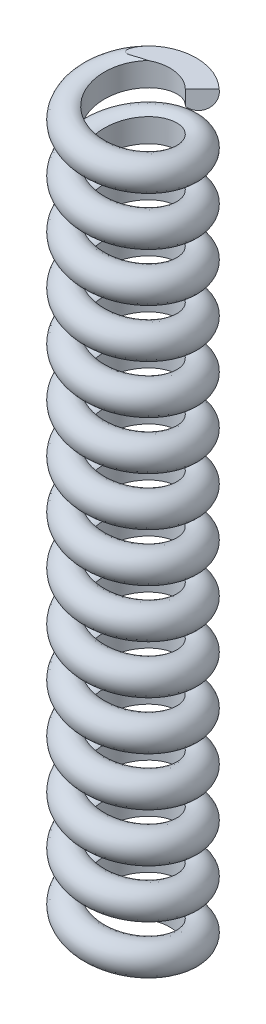
SolidWorks part; units mm, degrees
note: '?' marks a value the reader was unsure of.
material "1023 Carbon Steel Sheet (SS)"
ref_plane "Front" through (0, 0, 0) normal (0, 0, 1) x (1, 0, 0)
ref_plane "Top" through (0, 0, 0) normal (0, 1, 0) x (1, 0, 0)
ref_plane "Right" through (0, 0, 0) normal (1, 0, 0) x (0, 0, -1)
sketch "Sketch1" plane through (0, 0, 0) normal (0, 1, 0) x (1, 0, 0)
  circle A0 centre (0, 0) radius 3.9688
  point P4 (0, 0)
  dimension "D1" = 7.9375
curve "Helix/Spiral1" pitch 4.1639 height 63.5 turns 15.25
sweep "Sweep1" add path "Helix/Spiral1" circular profile diameter 2.54 parameters "D3"=2.54
sketch "Sketch17" [suppressed] plane through (0, 0, 0) normal (0, 1, 0) x (1, 0, 0)
  circle A0 centre (0, 0) radius 3.9688
  dimension "D1" = 7.9375
curve "Helix/Spiral2" [suppressed] pitch 2.4984 height 38.1 turns 15.25
sweep "Sweep3" [suppressed] add path "Helix/Spiral2"? parameters "D3"=2.54
sketch "Sketch10" plane through (0, 0, 0) normal (1, 0, 0) x (0, 0, -1)
  line L0 (-10.2667, 63.5) -> (-10.2667, 38.1003)
  line L5 (-10.2667, 107.0699) -> (15.8793, 107.0699)
  line L6 (-10.2667, 107.0699) -> (-10.2667, 63.5)
  line L7 (-10.2667, 63.5) -> (15.8793, 63.5) construction
  line L8 (15.8793, 107.0699) -> (15.8793, 63.5)
  line L9 (-7.3012, 0) -> (8.8113, 0)
  line L10 (-7.3012, 0) -> (-7.3012, -4.697)
  line L11 (-7.3012, -4.697) -> (8.8113, -4.697)
  line L12 (8.8113, 0) -> (8.8113, -4.697)
  line L13 (-10.2667, 38.1003) -> (15.8793, 38.1003)
  line L14 (15.8793, 38.1003) -> (15.8793, 63.5)
  spline S0 degree 3 poles (2.8063, 0) (3.1714, 0.0862) (3.7631, 0.2605) (4.0718, 0.5204) (3.7622, 0.7808) (2.8794, 1.041) (1.5583, 1.3012) (0, 1.5615) (-1.5583, 1.8217) (-2.8794, 2.082) (-3.7621, 2.3422) (-4.0721, 2.6025) (-3.7621, 2.8627) (-2.8794, 3.123) (-1.118, 3.4699) (1.118, 3.8169) (2.8794, 4.1639) (3.7621, 4.4242) (4.0721, 4.6844) (3.7621, 4.9447) (2.8794, 5.2049) (1.118, 5.5519) (-1.118, 5.8989) (-2.8794, 6.2459) (-3.7621, 6.5061) (-4.0721, 6.7664) (-3.7621, 7.0266) (-2.8794, 7.2869) (-1.118, 7.6339) (1.118, 7.9809) (2.8794, 8.3279) (3.7621, 8.5881) (4.0721, 8.8484) (3.7621, 9.1086) (2.8794, 9.3689) (1.118, 9.7158) (-1.118, 10.0628) (-2.8794, 10.4098) (-3.7621, 10.6701) (-4.0721, 10.9303) (-3.7621, 11.1906) (-2.8794, 11.4508) (-1.118, 11.7978) (1.118, 12.1448) (2.8794, 12.4918) (3.7621, 12.752) (4.0721, 13.0123) (3.7621, 13.2725) (2.8794, 13.5328) (1.118, 13.8798) (-1.118, 14.2268) (-2.8794, 14.5738) (-3.7621, 14.834) (-4.0721, 15.0943) (-3.7621, 15.3545) (-2.8794, 15.6148) (-1.118, 15.9617) (1.118, 16.3087) (2.8794, 16.6557) (3.7621, 16.916) (4.0721, 17.1762) (3.7621, 17.4365) (2.8794, 17.6967) (1.118, 18.0437) (-1.118, 18.3907) (-2.8794, 18.7377) (-3.7621, 18.998) (-4.0721, 19.2582) (-3.7621, 19.5184) (-2.8794, 19.7787) (-1.118, 20.1257) (1.118, 20.4727) (2.8794, 20.8197) (3.7621, 21.0799) (4.0721, 21.3402) (3.7621, 21.6004) (2.8794, 21.8607) (1.118, 22.2077) (-1.118, 22.5546) (-2.8794, 22.9016) (-3.7621, 23.1619) (-4.0721, 23.4221) (-3.7621, 23.6824) (-2.8794, 23.9426) (-1.118, 24.2896) (1.118, 24.6366) (2.8794, 24.9836) (3.7621, 25.2439) (4.0721, 25.5041) (3.7621, 25.7643) (2.8794, 26.0246) (1.118, 26.3716) (-1.118, 26.7186) (-2.8794, 27.0656) (-3.7621, 27.3258) (-4.0721, 27.5861) (-3.7621, 27.8463) (-2.8794, 28.1066) (-1.118, 28.4536) (1.118, 28.8005) (2.8794, 29.1475) (3.7621, 29.4078) (4.0721, 29.668) (3.7621, 29.9283) (2.8794, 30.1885) (1.118, 30.5355) (-1.118, 30.8825) (-2.8794, 31.2295) (-3.7621, 31.4898) (-4.0721, 31.75) (-3.7621, 32.0102) (-2.8794, 32.2705) (-1.118, 32.6175) (1.118, 32.9645) (2.8794, 33.3115) (3.7621, 33.5717) (4.0721, 33.832) (3.7621, 34.0922) (2.8794, 34.3525) (1.118, 34.6995) (-1.118, 35.0464) (-2.8794, 35.3934) (-3.7621, 35.6537) (-4.0721, 35.9139) (-3.7621, 36.1742) (-2.8794, 36.4344) (-1.118, 36.7814) (1.118, 37.1284) (2.8794, 37.4754) (3.7621, 37.7357) (4.0721, 37.9959) (3.7621, 38.2561) (2.8794, 38.5164) (1.118, 38.8634) (-1.118, 39.2104) (-2.8794, 39.5574) (-3.7621, 39.8176) (-4.0721, 40.0779) (-3.7621, 40.3381) (-2.8794, 40.5984) (-1.118, 40.9454) (1.118, 41.2923) (2.8794, 41.6393) (3.7621, 41.8996) (4.0721, 42.1598) (3.7621, 42.4201) (2.8794, 42.6803) (1.118, 43.0273) (-1.118, 43.3743) (-2.8794, 43.7213) (-3.7621, 43.9816) (-4.0721, 44.2418) (-3.7621, 44.502) (-2.8794, 44.7623) (-1.118, 45.1093) (1.118, 45.4563) (2.8794, 45.8033) (3.7621, 46.0635) (4.0721, 46.3238) (3.7621, 46.584) (2.8794, 46.8443) (1.118, 47.1913) (-1.118, 47.5383) (-2.8794, 47.8852) (-3.7621, 48.1455) (-4.0721, 48.4057) (-3.7621, 48.666) (-2.8794, 48.9262) (-1.118, 49.2732) (1.118, 49.6202) (2.8794, 49.9672) (3.7621, 50.2275) (4.0721, 50.4877) (3.7621, 50.748) (2.8794, 51.0082) (1.118, 51.3552) (-1.118, 51.7022) (-2.8794, 52.0492) (-3.7621, 52.3094) (-4.0721, 52.5697) (-3.7621, 52.8299) (-2.8794, 53.0902) (-1.118, 53.4372) (1.118, 53.7842) (2.8794, 54.1311) (3.7621, 54.3914) (4.0721, 54.6516) (3.7621, 54.9119) (2.8794, 55.1721) (1.118, 55.5191) (-1.118, 55.8661) (-2.8794, 56.2131) (-3.7621, 56.4734) (-4.0721, 56.7336) (-3.7621, 56.9939) (-2.8794, 57.2541) (-1.118, 57.6011) (1.118, 57.9481) (2.8794, 58.2951) (3.7621, 58.5553) (4.0721, 58.8156) (3.7621, 59.0758) (2.8794, 59.3361) (1.118, 59.6831) (-1.118, 60.0301) (-2.8794, 60.377) (-3.7621, 60.6373) (-4.0721, 60.8975) (-3.7621, 61.1578) (-2.8794, 61.418) (-1.5583, 61.6783) (0, 61.9385) (1.5583, 62.1988) (2.8794, 62.459) (3.7622, 62.7192) (4.0718, 62.9796) (3.7631, 63.2395) (3.1714, 63.4138) (2.8063, 63.5) knots 0 0 0 0 0.004098 0.008197 0.012295 0.016393 0.020492 0.02459 0.028689 0.032787 0.036885 0.040984 0.045082 0.04918 0.053279 0.061475 0.065574 0.069672 0.07377 0.077869 0.081967 0.086066 0.094262 0.098361 0.102459 0.106557 0.110656 0.114754 0.118852 0.127049 0.131148 0.135246 0.139344 0.143443 0.147541 0.151639 0.159836 0.163934 0.168033 0.172131 0.17623 0.180328 0.184426 0.192623 0.196721 0.20082 0.204918 0.209016 0.213115 0.217213 0.22541 0.229508 0.233607 0.237705 0.241803 0.245902 0.25 0.258197 0.262295 0.266393 0.270492 0.27459 0.278689 0.282787 0.290984 0.295082 0.29918 0.303279 0.307377 0.311475 0.315574 0.32377 0.327869 0.331967 0.336066 0.340164 0.344262 0.348361 0.356557 0.360656 0.364754 0.368852 0.372951 0.377049 0.381148 0.389344 0.393443 0.397541 0.401639 0.405738 0.409836 0.413934 0.422131 0.42623 0.430328 0.434426 0.438525 0.442623 0.446721 0.454918 0.459016 0.463115 0.467213 0.471311 0.47541 0.479508 0.487705 0.491803 0.495902 0.5 0.504098 0.508197 0.512295 0.520492 0.52459 0.528689 0.532787 0.536885 0.540984 0.545082 0.553279 0.557377 0.561475 0.565574 0.569672 0.57377 0.577869 0.586066 0.590164 0.594262 0.598361 0.602459 0.606557 0.610656 0.618852 0.622951 0.627049 0.631148 0.635246 0.639344 0.643443 0.651639 0.655738 0.659836 0.663934 0.668033 0.672131 0.67623 0.684426 0.688525 0.692623 0.696721 0.70082 0.704918 0.709016 0.717213 0.721311 0.72541 0.729508 0.733607 0.737705 0.741803 0.75 0.754098 0.758197 0.762295 0.766393 0.770492 0.77459 0.782787 0.786885 0.790984 0.795082 0.79918 0.803279 0.807377 0.815574 0.819672 0.82377 0.827869 0.831967 0.836066 0.840164 0.848361 0.852459 0.856557 0.860656 0.864754 0.868852 0.872951 0.881148 0.885246 0.889344 0.893443 0.897541 0.901639 0.905738 0.913934 0.918033 0.922131 0.92623 0.930328 0.934426 0.938525 0.946721 0.95082 0.954918 0.959016 0.963115 0.967213 0.971311 0.97541 0.979508 0.983607 0.987705 0.991803 0.995902 1 1 1 1 construction
  point P8 (2.8063, 63.5)
  point P9 (2.8063, 0)
  point P12 (2.8063, 63.5)
  dimension "D1" = 63.5
extrude "TopandBottom" [suppressed] cut sketch "Sketch10" against normal through all both and the other way through all
sketch "Sketch13" plane through (0, 0, 0) normal (0, 1, 0) x (1, 0, 0)
  circle A0 centre (0, 0) radius 3.175
  dimension "D1" = 6.35
extrude "CentralHole" cut sketch "Sketch13" against normal through all both and the other way through all
sketch "Sketch18" plane through (0, 0, 0) normal (0, 0, 1) x (1, 0, 0)
  line L1 (-9.4092, -0.1693) -> (16.579, -0.1693)
  line L2 (-9.4092, -0.1693) -> (-9.4092, -6.5182)
  line L3 (-9.4092, -6.5182) -> (16.579, -6.5182)
  line L4 (16.579, -0.1693) -> (16.579, -6.5182)
  line L5 (19.6687, 63.6693) -> (-15.3042, 63.6693)
  line L6 (19.6687, 63.6693) -> (19.6687, 73.8461)
  line L7 (19.6687, 73.8461) -> (-15.3042, 73.8461)
  line L8 (-15.3042, 63.6693) -> (-15.3042, 73.8461)
  ellipse E0 centre (2.8063, 63.5) end of major axis (3.0982, 62.264) minor radius 0.8858 (2.3572, 62.5255) -> (2.127, 64.4745) ccw construction
  ellipse E1 centre (-2.8063, 0) end of major axis (-2.5144, -1.236) minor radius 0.8858 (-2.3572, 0.9745) -> (-2.127, -0.9745) ccw construction
  point P16 (3.6761, 63.6693)
  point P24 (-3.6761, -0.1693)
extrude "Cut-Extrude1" cut sketch "Sketch18" against normal through all both and the other way through all
